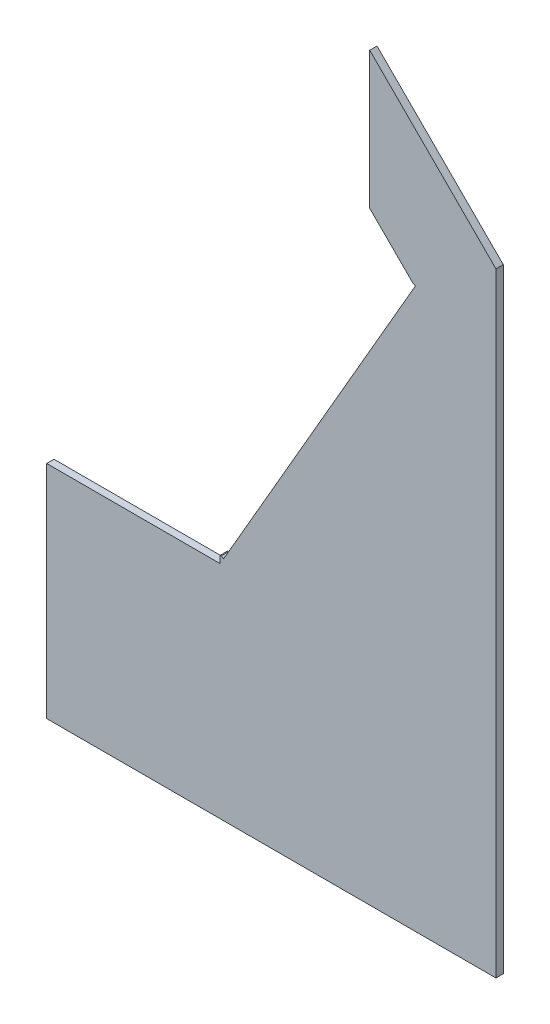
SolidWorks part; units mm, degrees
ref_plane "Front Plane" through (0, 0, 0) normal (0, 0, 1) x (1, 0, 0)
ref_plane "Top Plane" through (0, 0, 0) normal (0, 1, 0) x (1, 0, 0)
ref_plane "Right Plane" through (0, 0, 0) normal (1, 0, 0) x (0, 0, -1)
sketch "Sketch1" plane through (0, 0, 0) normal (0, 0, 1) x (1, 0, 0)
  line L0 (0, 242) -> (190, 242) construction
  line L1 (0, 0) -> (492, 0)
  line L2 (0, 0) -> (0, 242)
  line L3 (0, 242) -> (190, 242)
  line L5 (190, 242) -> (403.25, 611.3598)
  line L6 (403.25, 611.3598) -> (353.7525, 660.8573)
  line L7 (353.7525, 660.8573) -> (353.7525, 810.8573)
  line L8 (353.7525, 810.8573) -> (492, 672.6098)
  line L9 (492, 672.6098) -> (492, 0)
  line L10 (190, 242) -> (190, 250)
  line L11 (190, 250) -> (191.15, 250)
  line L12 (191.15, 250) -> (193.7516, 248.498)
  line L13 (403.25, 611.3598) -> (403.7516, 612.2286)
  line L14 (403.7516, 612.2286) -> (401.1535, 613.7286)
  line L15 (401.1535, 613.7286) -> (401.0538, 613.556)
  line L16 (191.1535, 249.998) -> (401.1535, 613.7286) construction
  dimension "D3" = 60
  dimension "D1" = 492
  dimension "D2" = 242
  dimension "D4" = 426.5
  dimension "D5" = 190
  dimension "D6" = 150
  dimension "D7" = 70
  dimension "D8" = 105
  dimension "D9" = 8
  dimension "D10" = 1.15
extrude "Boss-Extrude1" add sketch "Sketch1" along normal blind 8 contours L12 L11 L10 L5 | L15 L14 L13 L5 L3 L2 L1 L9 L8 L7 L6 region at (307.6187, 261.0601, 0) region at (191.2714, 246.9778, 0)
